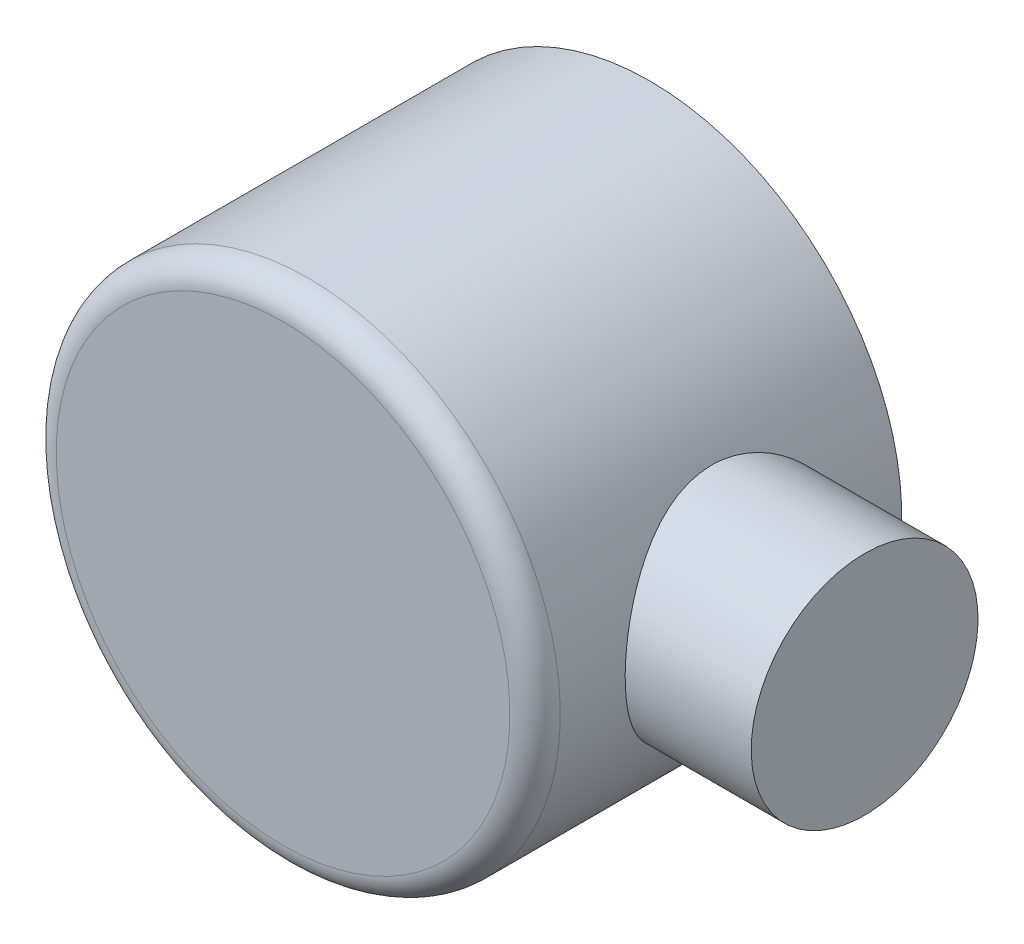
SolidWorks part; units mm, degrees
material "Cast Stainless Steel"
ref_plane "Front Plane" through (0, 0, 0) normal (0, 0, 1) x (1, 0, 0)
ref_plane "Top Plane" through (0, 0, 0) normal (0, 1, 0) x (1, 0, 0)
ref_plane "Right Plane" through (0, 0, 0) normal (1, 0, 0) x (0, 0, -1)
other "Center of Mass"
sketch "Sketch2" plane through (0, 0, 0) normal (1, 0, 0) x (0, 0, -1)
  circle A0 centre (0, 0) radius 50
  dimension "D1" = 100
extrude "Boss-Extrude1" add sketch "Sketch2" along normal blind 64.75
ref_plane "Plane1" through (32.375, 0, 0) normal (-1, 0, 0) x (0, 0, 1)
sketch "Sketch3" plane through (32.375, 0, 0) normal (-1, 0, 0) x (0, 0, 1)
  line L0 (0, 50) -> (0, 75)
  line L1 (0, 75) -> (22.5, 75)
  line L2 (0, 75) -> (-22.5, 75)
  line L3 (-22.5, 75) -> (-22.5, 44.6514)
  line L4 (22.5, 75) -> (22.5, 44.6514)
  circle A1 centre (0, 0) radius 50
  circle A2 centre (0, 0) radius 50
  dimension "D2" = 25
  dimension "D3" = 22.5
  dimension "D4" = 22.5
  dimension "D1" = 0
revolve "Revolve1" add sketch "Sketch3" angle 360 about L0 region at (32.375, 61.5818, 11.6206)
sketch "Sketch4" plane through (0, 0, 0) normal (-1, 0, 0) x (0, 0, 1)
  circle A1 centre (0, 0) radius 50
  circle A2 centre (0, 0) radius 50
  dimension "D1" = 0
extrude "Boss-Extrude2" add sketch "Sketch4" along normal blind 8
fillet "Fillet1" radius 5 1 edges at (-8, 0, 50)
ref_plane "Plane3" through (32.38, 0, 0) normal (-1, 0, 0) x (0, 0, 1)
ref_axis "Axis2" through (32.375, 75, 0) along (0, -1, 0)
ref_axis "Axis3" through (64.75, 0, 0) along (-1, 0, 0)
ref_point "Point1"
move or copy body "Body-Move/Copy1" bodies to move or copy 103 copy no translate (-32.38, 0, 0)
move or copy body "Body-Move/Copy2" bodies to move or copy 107 copy no rotation origin (0, 0, 0) rotation axis (0.5774, 0.5774, -0.5774) rotation angle 120
sketch "Sketch5" plane through (0, 0, -32.37) normal (0, 0, -1) x (-1, 0, 0)
  circle A0 centre (0, 0) radius 42.5
  dimension "D1" = 85
extrude "Cut-Extrude1" cut sketch "Sketch5" against normal blind 60
